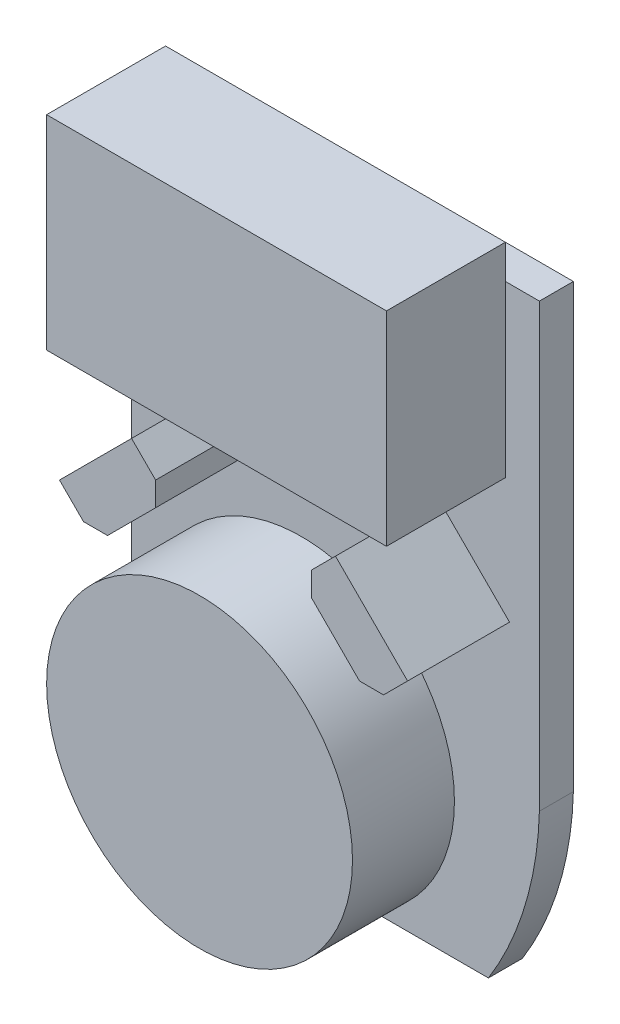
SolidWorks part; units mm, degrees
ref_plane "Plan de face" through (0, 0, 0) normal (0, 0, 1) x (1, 0, 0)
ref_plane "Plan de dessus" through (0, 0, 0) normal (0, 1, 0) x (1, 0, 0)
ref_plane "Plan de droite" through (0, 0, 0) normal (1, 0, 0) x (0, 0, -1)
sketch "Esquisse1" plane through (0, 0, 0) normal (0, 0, 1) x (1, 0, 0)
  line L0 (-6, 0) -> (6, 0) construction
  line L1 (-6, 0) -> (-6, 13)
  line L2 (0, -7.6278) -> (0, 15.9086) construction
  line L3 (-6, 13) -> (6, 13)
  line L4 (-4.5, -5) -> (4.5, -5)
  line L5 (-3.9073, -4.5) -> (4.16, -4.5) construction
  line L6 (0, 13) -> (0, -5)
  line L7 (6, 0) -> (6, 13)
  line L9 (-5, 14) -> (5, 14)
  line L10 (-5, 14) -> (-5, 8)
  line L11 (-5, 8) -> (5, 8)
  line L12 (5, 14) -> (5, 8)
  line L13 (-5, 14) -> (5, 8) construction
  line L14 (-5, 8) -> (5, 14) construction
  circle A1 centre (0, 0) radius 4.5
  arc A2 (-6, 0) -> (-4.5, -5) centre (3.9962, 0.2739) ccw
  arc A3 (6, 0) -> (4.5, -5) centre (-3.9962, 0.2739) cw
  circle A4 centre (0, 0) radius 0.5
  point P6 (0, 0)
  point P23 (0, 11)
  dimension "D1" = 4.5
  dimension "D5" = 10
  dimension "D10" = 1
  dimension "D2" = 12
  dimension "D3" = 18
  dimension "D4" = 0.5
  dimension "D6" = 9
  dimension "D7" = 10
  dimension "D8" = 6
  dimension "D9" = 1
extrude "Boss.-Extru.1" add sketch "Esquisse1" along normal blind 1 contours A3 L4 A2 L1 L3 L7
extrude "Boss.-Extru.2" add sketch "Esquisse1<4>" along normal blind 1 from surface contours L6 A4 | L6 A4 region at (-0.2122, 0, 0) region at (0.2122, 0, 0) starting at face at (0, 2.6335, 1)
sketch "Esquisse1<4>" plane through (0, 0, 0) normal (0, 0, 1) x (1, 0, 0) same geometry as "Esquisse1"
extrude "Boss.-Extru.3" add sketch "Esquisse1<5>" along normal blind 3 from surface contours A4 L6 A1 | A4 L6 A1 | L6 A4 | L6 A4 region at (-1.9311, 0, 0) region at (1.9311, 0, 0) region at (-0.2122, 0, 0) region at (0.2122, 0, 0) starting at face at (0.5, 0, 2)
sketch "Esquisse1<5>" plane through (0, 0, 0) normal (0, 0, 1) x (1, 0, 0) same geometry as "Esquisse1"
extrude "Boss.-Extru.4" add sketch "Esquisse1<6>" along normal blind 3.5 from surface contours L11 L12 L9 L10 starting at face at (0.5, 0, 1)
sketch "Esquisse1<6>" plane through (0, 0, 0) normal (0, 0, 1) x (1, 0, 0) same geometry as "Esquisse1"
sketch "Esquisse2" plane through (0, 0, 1) normal (0, 0, 1) x (1, 0, 0)
  line L0 (0, 0) -> (0, 10.7905) construction
  line L1 (-5.1213, 4.3787) -> (-3, 6.5)
  line L2 (-3, 6.5) -> (-2.2929, 5.7929)
  line L3 (-2.2929, 5.7929) -> (-2.2929, 5.0858)
  line L4 (-2.2929, 5.0858) -> (-3.7071, 3.6716)
  line L5 (-3.7071, 3.6716) -> (-4.4142, 3.6716)
  line L6 (-4.4142, 3.6716) -> (-5.1213, 4.3787)
  line L7 (0, 6.5) -> (-3, 6.5) construction
  point P5 (-4.4142, 3.707)
  dimension "D1" = 3
  dimension "D2" = 1.5
  dimension "D3" = 1
  dimension "D4" = 2
  dimension "D5" = 45
  dimension "D6" = 3
  dimension "D7" = 6.5
extrude "Boss.-Extru.5" add sketch "Esquisse2" along normal blind 3
mirror "Symétrie1" about plane through (0, 0, 0) normal (1, 0, 0) of "Boss.-Extru.5"
